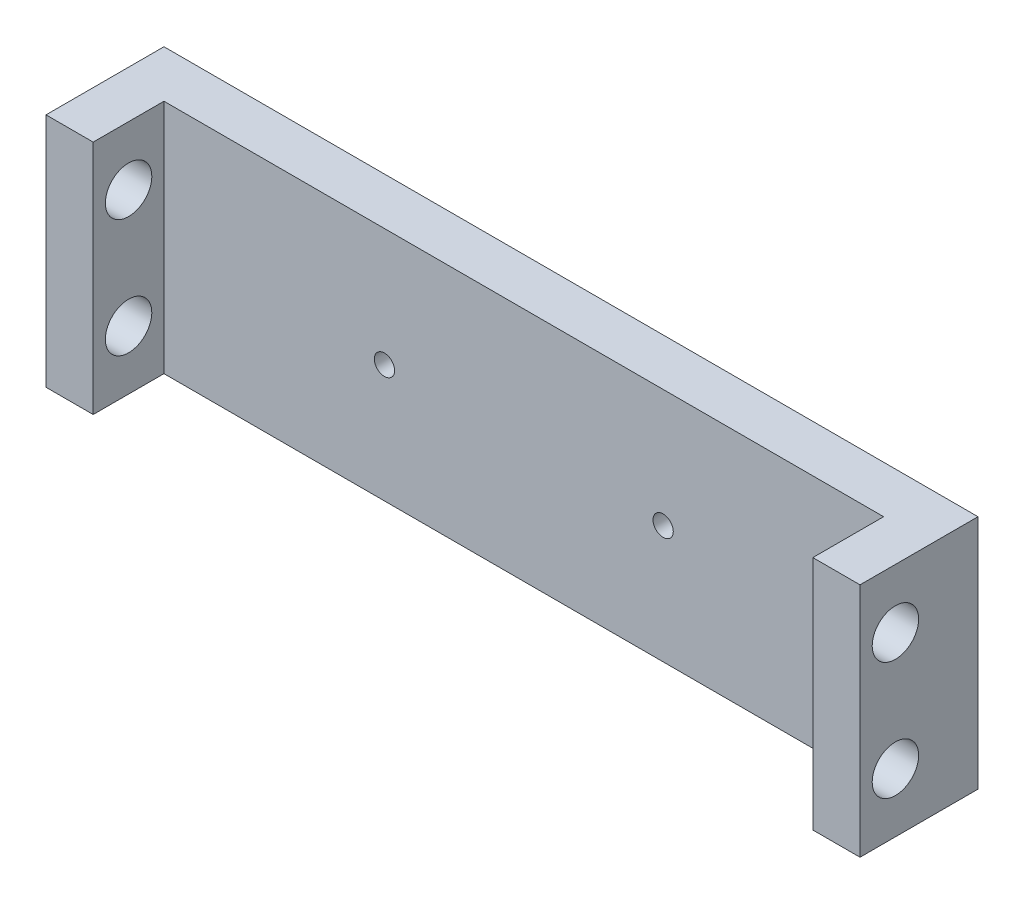
SolidWorks part; units mm, degrees
material "ABS"
ref_plane "Front Plane" through (0, 0, 0) normal (0, 0, 1) x (1, 0, 0)
ref_plane "Top Plane" through (0, 0, 0) normal (0, 1, 0) x (1, 0, 0)
ref_plane "Right Plane" through (0, 0, 0) normal (1, 0, 0) x (0, 0, -1)
sketch "Sketch1" plane through (0, 0, 0) normal (0, 0, 1) x (1, 0, 0)
  line L0 (82.55, 25.4) -> (82.55, 0)
  line L1 (0, 0) -> (87.63, 0)
  line L2 (0, 0) -> (0, 25.4)
  line L3 (0, 25.4) -> (87.63, 25.4)
  line L4 (87.63, 0) -> (87.63, 25.4)
  line L5 (5.08, 25.4) -> (5.08, 0)
  line L6 (5.08, 12.7) -> (82.55, 12.7) construction
  circle A0 centre (28.815, 12.7) radius 1.0922
  circle A1 centre (58.815, 12.7) radius 1.0922
  point P15 (43.815, 12.7)
  dimension "D3" = 30
  dimension "D6" = 2.1844
  dimension "D1" = 5.08
  dimension "D2" = 5.08
  dimension "D4" = 87.63
  dimension "D5" = 15
  dimension "D7" = 25.4
extrude "Boss-Extrude1" add sketch "Sketch1" along normal blind 5.08 contours L5 L6 A0 A1 L0 L3 | L6 L5 L1 L0 A1 A0 region at (43.815, 19.0725, 0) region at (43.815, 6.3275, 0)
extrude "Boss-Extrude2" add sketch "Sketch1<3>" along normal blind 12.7 contours L1 L4 L3 L0 | L5 L3 L2 L1 region at (85.09, 12.7, 0) region at (2.54, 12.7, 0)
sketch "Sketch1<3>" plane through (0, 0, 0) normal (0, 0, 1) x (1, 0, 0) same geometry as "Sketch1"
sketch "Sketch2" plane through (82.55, 0, 0) normal (-1, 0, 0) x (0, 0, 1)
  line L0 (8.89, 25.4) -> (8.89, 0) construction
  line L1 (12.7, 25.4) -> (5.08, 25.4) construction
  line L2 (12.7, 0) -> (5.08, 0) construction
  circle A0 centre (8.89, 19.05) radius 2.5
  circle A1 centre (8.89, 6.35) radius 2.5
  point P12 (8.89, 12.7)
  dimension "D1" = 12.7
  dimension "D2" = 6.35
  dimension "D3" = 5
extrude "Cut-Extrude1" cut sketch "Sketch2" along normal through all both and the other way through all
